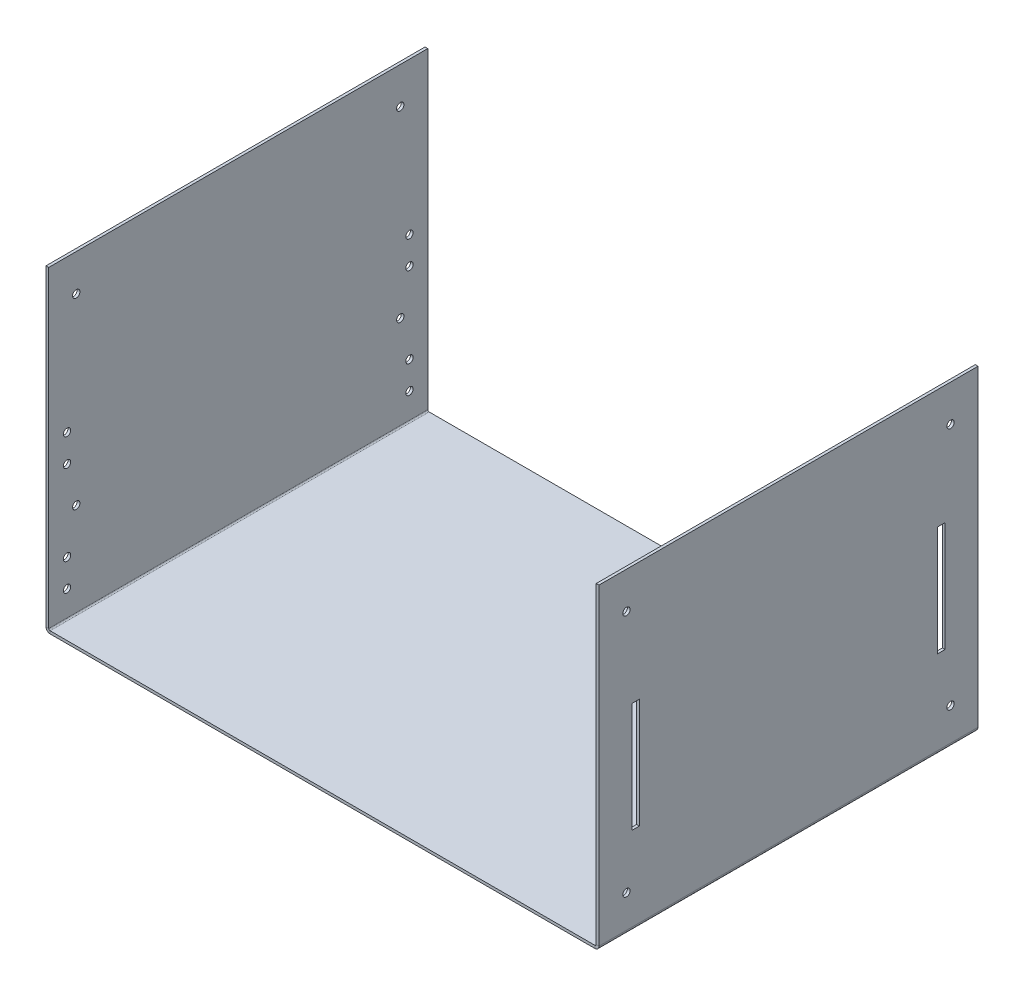
SolidWorks part; units mm, degrees
note: The reader was unsure of these and kept them because the rebuilt part matched: thickness of "Базовая кромка1", "Ребро-кромка1", "Листовой металл3", "Листовой металл4", "Листовой металл5", "Листовой металл6", "Листовой металл7", "Листовой металл8"; flange length of "Ребро-кромка1".
ref_plane "Спереди" through (0, 0, 0) normal (0, 0, 1) x (1, 0, 0)
ref_plane "Сверху" through (0, 0, 0) normal (0, 1, 0) x (1, 0, 0)
ref_plane "Справа" through (0, 0, 0) normal (1, 0, 0) x (0, 0, -1)
sketch "Эскиз1" plane through (0, 0, 0) normal (0, 1, 0) x (1, 0, 0)
  line L1 (0, 0) -> (302, 0)
  line L2 (0, 0) -> (0, 207)
  line L3 (0, 207) -> (302, 207)
  line L4 (302, 0) -> (302, 207)
  dimension "D1" = 302
  dimension "D2" = 207
base flange "Базовая кромка1" sketch "Эскиз1" thickness 1.5 reverse thickness direction no parameters "D1"=0.7366
edge flange "Ребро-кромка1" sketch "Эскиз10" flange profiles "Эскиз10", "Эскиз11" flange angle 90 flange length 173 flange position material inside bend radius 0.7366 thickness 1.5 relief rectangular parameters "D6"=10, "D8"=1
sketch "Эскиз10" plane through (0, 0, 0) normal (-1, 0, 0) x (0, 0, 1)
  line L0 (-207, 0) -> (0, 0) construction
  line L1 (-207, 0) -> (0, 0)
  line L2 (-207, 0) -> (-207, 171.5)
  line L3 (-207, 171.5) -> (0, 171.5)
  line L4 (0, 171.5) -> (0, 0)
sketch "Эскиз11" plane through (302, 0, 0) normal (1, 0, 0) x (0, 0, -1)
  line L0 (0, 0) -> (207, 0) construction
  line L1 (0, 0) -> (207, 0)
  line L2 (0, 0) -> (0, 171.5)
  line L3 (0, 171.5) -> (207, 171.5)
  line L4 (207, 171.5) -> (207, 0)
bend "EdgeBend1" bend radius 0.7366 bend angle 90 parameters "D5"=1
bend "EdgeBend2" bend radius 0.7366 bend angle 90 parameters "D5"=2
sketch "Эскиз12" plane through (302, 0, 0) normal (1, 0, 0) x (0, 0, -1)
  line L0 (207, 171.5) -> (0, 171.5) construction
  line L1 (189, 106.5) -> (185, 106.5)
  line L2 (189, 106.5) -> (189, 46.5)
  line L3 (189, 46.5) -> (185, 46.5)
  line L4 (185, 106.5) -> (185, 46.5)
  line L6 (207, 0.7366) -> (207, 171.5) construction
  line L7 (22, 106.5) -> (18, 106.5)
  line L8 (22, 106.5) -> (22, 46.5)
  line L9 (22, 46.5) -> (18, 46.5)
  line L10 (18, 106.5) -> (18, 46.5)
  line L11 (0, 171.5) -> (0, 0.7366) construction
  dimension "D1" = 18
  dimension "D2" = 4
  dimension "D3" = 60
  dimension "D4" = 65
  dimension "D5" = 18
  dimension "D6" = 4
  dimension "D7" = 65
  dimension "D8" = 60
extrude "Вырез-Вытянуть1" cut sketch "Эскиз12" against normal up to next normal cut yes
sketch "Эскиз13" plane through (0, 0, 0) normal (-1, 0, 0) x (0, 0, 1)
  line L0 (-197, 88.5) -> (-197, 14.5) construction
  line L1 (-197, 14.5) -> (-10, 14.5) construction
  line L2 (-10, 14.5) -> (-10, 88.5) construction
  line L3 (-10, 88.5) -> (-197, 88.5) construction
  line L4 (0, 171.5) -> (-207, 171.5) construction
  line L5 (0, -1.5) -> (-207, -1.5) construction
  line L6 (-207, 171.5) -> (-207, 0.7366) construction
  line L8 (0, 0.7366) -> (0, 171.5) construction
  line L9 (-197, 73.5) -> (-10, 73.5) construction
  line L11 (-197, 29.5) -> (-10, 29.5) construction
  circle A0 centre (-197, 88.5) radius 2
  circle A1 centre (-197, 73.5) radius 2
  circle A2 centre (-197, 29.5) radius 2
  circle A3 centre (-197, 14.5) radius 2
  circle A4 centre (-10, 14.5) radius 2
  circle A5 centre (-10, 29.5) radius 2
  circle A6 centre (-10, 73.5) radius 2
  circle A7 centre (-10, 88.5) radius 2
  dimension "D7" = 4
  dimension "D1" = 83
  dimension "D2" = 16
  dimension "D3" = 10
  dimension "D4" = 10
  dimension "D5" = 15
  dimension "D6" = 15
extrude "Вырез-Вытянуть2" cut sketch "Эскиз13" against normal up to next normal cut yes
sketch "Эскиз14" plane through (0, 0, 0) normal (-1, 0, 0) x (0, 0, 1)
  line L0 (-192, 171.5) -> (-192, -1.5) construction
  line L1 (0, 171.5) -> (-207, 171.5) construction
  line L2 (0, -1.5) -> (-207, -1.5) construction
  line L3 (-207, 171.5) -> (-207, 0.7366) construction
  line L4 (-15, 171.5) -> (-15, -1.5) construction
  line L5 (0, 0.7366) -> (0, 171.5) construction
  line L6 (-192, 151.5) -> (-15, 151.5) construction
  line L7 (-192, 51.5) -> (-15, 51.5) construction
  circle A0 centre (-192, 151.5) radius 2
  circle A1 centre (-15, 151.5) radius 2
  circle A2 centre (-15, 51.5) radius 2
  circle A3 centre (-192, 51.5) radius 2
  dimension "D5" = 4
  dimension "D1" = 15
  dimension "D2" = 15
  dimension "D3" = 20
  dimension "D4" = 100
extrude "Вырез-Вытянуть3" cut sketch "Эскиз14" against normal up to next normal cut yes
sketch "Эскиз15" plane through (302, 0, 0) normal (1, 0, 0) x (0, 0, -1)
  line L0 (0, 151.5) -> (207, 151.5) construction
  line L1 (0, 171.5) -> (0, 0) construction
  line L2 (207, 0.7366) -> (207, 171.5) construction
  line L3 (0, 171.5) -> (0, 0.7366) construction
  line L4 (207, 0.7366) -> (0, 0.7366) construction
  line L5 (15, 0.7366) -> (15, 151.5) construction
  line L6 (207, 171.5) -> (0, 171.5) construction
  line L7 (192, 0.7366) -> (192, 151.5) construction
  line L8 (15, 18.5) -> (192, 18.5) construction
  line L9 (207, -1.5) -> (0, -1.5) construction
  circle A0 centre (15, 151.5) radius 2
  circle A1 centre (192, 151.5) radius 2
  circle A2 centre (15, 18.5) radius 2
  circle A3 centre (192, 18.5) radius 2
  dimension "D4" = 4
  dimension "D1" = 15
  dimension "D2" = 15
  dimension "D3" = 20
  dimension "D5" = 20
extrude "Вырез-Вытянуть4" cut sketch "Эскиз15" against normal up to next normal cut yes
sketch "Сгиб-Линии1"
sketch "Граничная рамка1" plane through (0, 0, 0) normal (0, 1, 0) x (1, 0, 0)
sheet metal parameters "Листовой металл3" thickness 1.5 parameters "D1"=0.7366
flat pattern "Развертка3" [suppressed]
sketch "Сгиб-Линии2" plane through (0, 0, 0) normal (0, 1, 0) x (1, 0, 0)
sketch "Граничная рамка2" [suppressed] plane through (0, 0, 0) normal (0, 1, 0) x (1, 0, 0)
sheet metal parameters "Листовой металл4" thickness 1.5 parameters "D1"=0.7366, "D7"=1
flat pattern "Развертка3" [suppressed]
sketch "Сгиб-Линии2" plane through (0, 0, 0) normal (0, 1, 0) x (1, 0, 0)
sketch "Граничная рамка2" [suppressed] plane through (0, 0, 0) normal (0, 1, 0) x (1, 0, 0)
bend of the flat pattern "Плоское состояние-<EdgeBend1>1"
bend of the flat pattern "Плоское состояние-<EdgeBend2>1"
sheet metal parameters "Листовой металл5" thickness 1.5 parameters "D1"=0.7366, "D7"=1
flat pattern "Развертка3" [suppressed]
sketch "Сгиб-Линии2" plane through (0, 0, 0) normal (0, 1, 0) x (1, 0, 0)
sketch "Граничная рамка2" [suppressed] plane through (0, 0, 0) normal (0, 1, 0) x (1, 0, 0)
bend of the flat pattern "Плоское состояние-<EdgeBend1>1"
bend of the flat pattern "Плоское состояние-<EdgeBend2>1"
sheet metal parameters "Листовой металл6" thickness 1.5 parameters "D1"=0.7366, "D7"=1
flat pattern "Развертка3" [suppressed]
sketch "Сгиб-Линии2" plane through (0, 0, 0) normal (0, 1, 0) x (1, 0, 0)
sketch "Граничная рамка2" [suppressed] plane through (0, 0, 0) normal (0, 1, 0) x (1, 0, 0)
bend of the flat pattern "Плоское состояние-<EdgeBend1>1"
bend of the flat pattern "Плоское состояние-<EdgeBend2>1"
sheet metal parameters "Листовой металл7" thickness 1.5 parameters "D1"=0.7366, "D7"=1
flat pattern "Развертка3" [suppressed]
sketch "Сгиб-Линии2" plane through (0, 0, 0) normal (0, 1, 0) x (1, 0, 0)
sketch "Граничная рамка2" [suppressed] plane through (0, 0, 0) normal (0, 1, 0) x (1, 0, 0)
bend of the flat pattern "Плоское состояние-<EdgeBend1>1"
bend of the flat pattern "Плоское состояние-<EdgeBend2>1"
sheet metal parameters "Листовой металл8" thickness 1.5 parameters "D1"=0.7366, "D7"=1
flat pattern "Развертка3" [suppressed]
sketch "Сгиб-Линии2" plane through (0, 0, 0) normal (0, 1, 0) x (1, 0, 0)
sketch "Граничная рамка2" [suppressed] plane through (0, 0, 0) normal (0, 1, 0) x (1, 0, 0)
bend of the flat pattern "Плоское состояние-<EdgeBend1>1"
bend of the flat pattern "Плоское состояние-<EdgeBend2>1"
